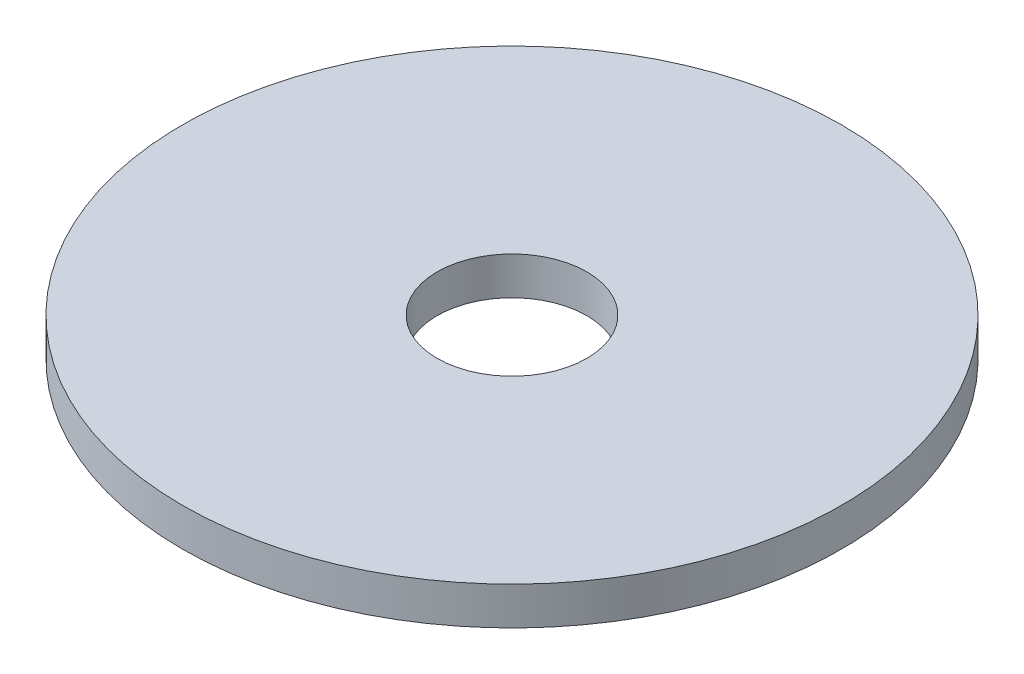
SolidWorks part; units mm, degrees
ref_plane "Front Plane" through (0, 0, 0) normal (0, 0, 1) x (1, 0, 0)
ref_plane "Top Plane" through (0, 0, 0) normal (0, 1, 0) x (1, 0, 0)
ref_plane "Right Plane" through (0, 0, 0) normal (1, 0, 0) x (0, 0, -1)
sketch "Sketch1" plane through (0, 0, 0) normal (0, 1, 0) x (1, 0, 0)
  circle A0 centre (0, 0) radius 83.82
  dimension "D1" = 167.64
extrude "Boss-Extrude1" add sketch "Sketch1" along normal mid plane 9.652
sketch "Sketch2" plane through (0, -4.826, 0) normal (0, -1, 0) x (1, 0, 0)
  circle A0 centre (0, 0) radius 19.05
  dimension "D1" = 38.1
extrude "Cut-Extrude1" cut sketch "Sketch2" against normal up to surface (9.652 mm away) up to face at (0, 4.826, 83.82)
